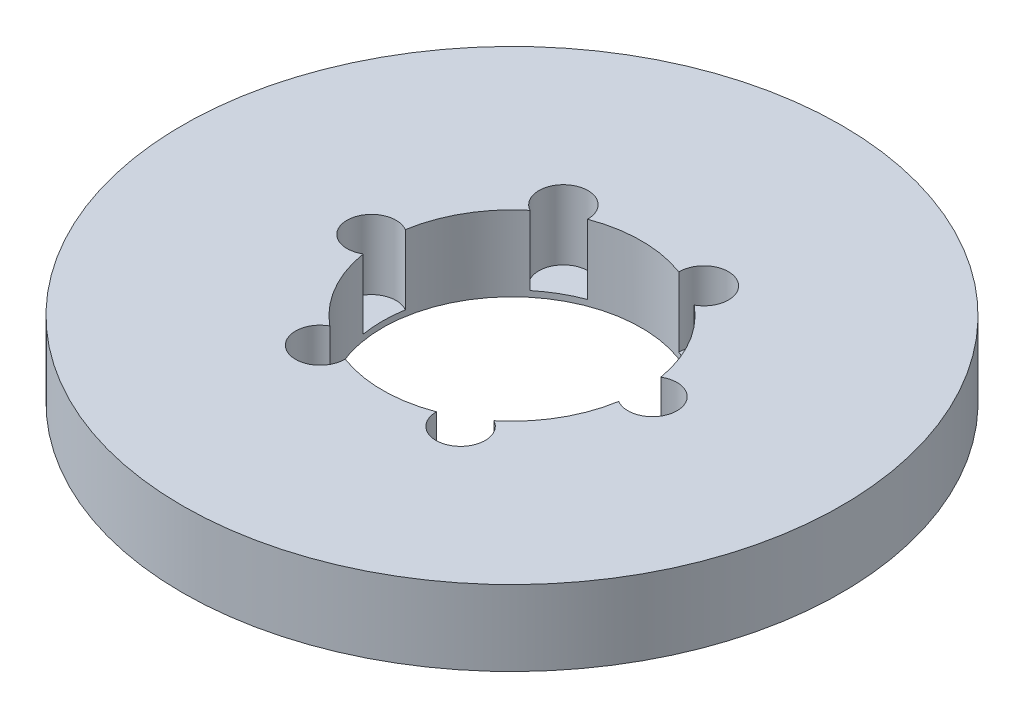
SolidWorks part; units mm, degrees
ref_plane "Front Plane" through (0, 0, 0) normal (0, 0, 1) x (1, 0, 0)
ref_plane "Top Plane" through (0, 0, 0) normal (0, 1, 0) x (1, 0, 0)
ref_plane "Right Plane" through (0, 0, 0) normal (1, 0, 0) x (0, 0, -1)
sketch "Sketch1" plane through (0, 0, 0) normal (0, 1, 0) x (1, 0, 0)
  circle A0 centre (0, 0) radius 70
  dimension "FLANGE_OD" = 140
extrude "Boss-Extrude1" add sketch "Sketch1" along normal blind 16
sketch "Sketch2" plane through (0, 0, 0) normal (0, 1, 0) x (1, 0, 0)
  circle A0 centre (0, 0) radius 27.5
  dimension "BORE_D" = 55
extrude "Cut-Extrude1" cut sketch "Sketch2" along normal through all
sketch "Sketch3" plane through (0, 16, 0) normal (0, 1, 0) x (1, 0, 0)
  circle A0 centre (0, 0) radius 29.839 construction
  circle A1 centre (-29.839, 0) radius 5.2196
  dimension "BOLT_D" = 10.4393
  dimension "BOLT_PCD" = 59.678
extrude "Cut-Extrude2" cut sketch "Sketch3" against normal blind 14.7611
pattern_circular "CirPattern1" count 6 over 360 about axis through (0, 0, 0) along (0, 1, 0) of "Cut-Extrude2"
